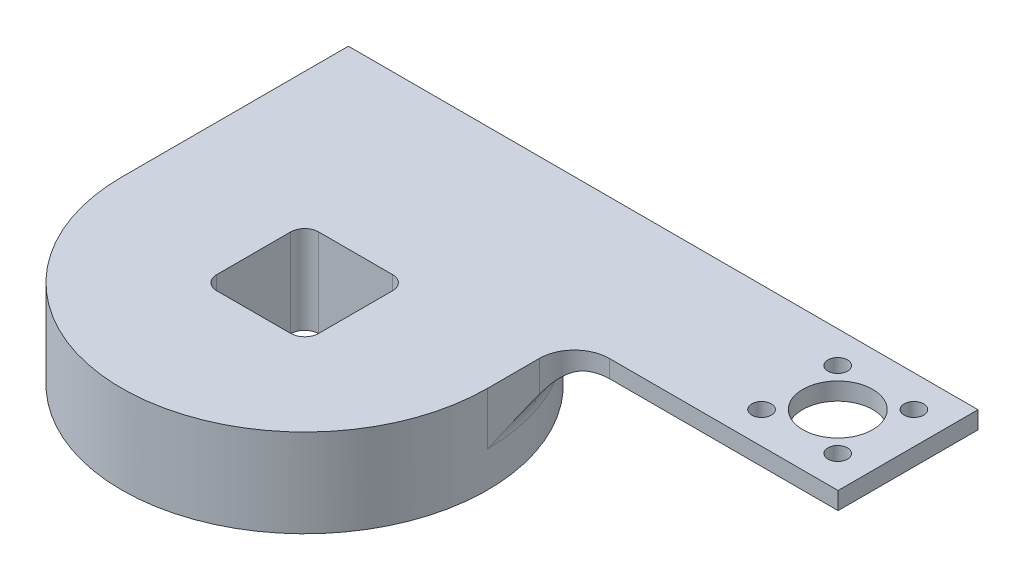
SolidWorks part; units mm, degrees
material "6061-T6 (SS)"
ref_plane "Front Plane" through (0, 0, 0) normal (0, 0, 1) x (1, 0, 0)
ref_plane "Top Plane" through (0, 0, 0) normal (0, 1, 0) x (1, 0, 0)
ref_plane "Right Plane" through (0, 0, 0) normal (1, 0, 0) x (0, 0, -1)
sketch "Sketch1" plane through (0, 0, 0) normal (0, 1, 0) x (1, 0, 0)
  line L0 (-1.1049, 0) -> (-33.2105, 0) construction
  line L1 (-1.1049, 0) -> (33.2105, 0) construction
  circle A0 centre (0, 0) radius 33.2105
  dimension "D1" = 66.421
extrude "Boss-Extrude1" add sketch "Sketch1" along normal blind 16.002
sketch "Sketch2" plane through (0, 16.002, 0) normal (0, 1, 0) x (1, 0, 0)
  line L0 (0, 0) -> (-33.2105, 0) construction
  line L1 (0, 0) -> (33.2105, 0) construction
  line L2 (-33.2105, 0) -> (-33.2105, 41.148)
  line L3 (-33.2105, 41.148) -> (81.0895, 41.148)
  line L4 (81.0895, 41.148) -> (81.0895, 15.748)
  line L5 (33.2105, 0) -> (33.2105, 15.748)
  line L6 (33.2105, 15.748) -> (81.0895, 15.748)
  circle A0 centre (0, 0) radius 33.2105 construction
  circle A2 centre (0, 0) radius 33.2105
  arc A3 (-33.2105, 0) -> (33.2105, 0) centre (0, 0) ccw
  dimension "D1" = 0
  dimension "D2" = 114.3
  dimension "D3" = 25.4
  dimension "D4" = 15.748
extrude "Boss-Extrude2" add sketch "Sketch2" against normal blind 3.175
fillet "Fillet1" radius 6.35 1 edges at (0, 12.827, -33.2105)
fillet "Fillet2" radius 6.35 1 edges at (33.2105, 14.0878, -15.748)
sketch "Sketch4" plane through (0, 16.002, 0) normal (0, 1, 0) x (1, 0, 0)
  line L0 (81.0895, 41.148) -> (58.166, 41.148) construction
  line L1 (81.0895, 41.148) -> (-33.2105, 41.148) construction
  line L2 (58.166, 41.148) -> (58.166, 28.448) construction
  line L3 (58.166, 28.448) -> (78.486, 28.448) construction
  line L4 (68.326, 28.448) -> (75.2408, 35.3628) construction
  line L5 (68.326, 28.448) -> (75.2408, 21.5332) construction
  line L6 (68.326, 28.448) -> (61.4112, 21.5332) construction
  line L7 (68.326, 28.448) -> (61.4112, 35.3628) construction
  circle A0 centre (61.4112, 35.3628) radius 1.778
  circle A1 centre (75.2408, 35.3628) radius 1.778
  circle A2 centre (75.2408, 21.5332) radius 1.778
  circle A3 centre (68.326, 28.448) radius 6.35
  circle A4 centre (61.4112, 21.5332) radius 1.778
extrude "Cut-Extrude2" cut sketch "Sketch4" against normal up to next
sketch "Sketch5" plane through (0, 16.002, 0) normal (0, 1, 0) x (1, 0, 0)
  line L1 (9.2497, 9.2497) -> (-9.2497, 9.2497)
  line L2 (9.2497, 9.2497) -> (9.2497, -9.2497)
  line L3 (9.2497, -9.2497) -> (-9.2497, -9.2497)
  line L4 (-9.2497, 9.2497) -> (-9.2497, -9.2497)
  line L5 (9.2497, 9.2497) -> (-9.2497, -9.2497) construction
  line L6 (9.2497, -9.2497) -> (-9.2497, 9.2497) construction
  point P0 (0, 0)
  dimension "D1" = 26.162
extrude "Cut-Extrude3" cut sketch "Sketch5" against normal up to next
fillet "Fillet3" radius 2.54 1 edges at (-9.2497, 8.001, -9.2497)
fillet "Fillet4" radius 2.54 1 edges at (9.2497, 8.001, -9.2497)
fillet "Fillet5" radius 2.54 1 edges at (9.2497, 8.001, 9.2497)
fillet "Fillet6" radius 2.54 1 edges at (-9.2497, 8.001, 9.2497)
